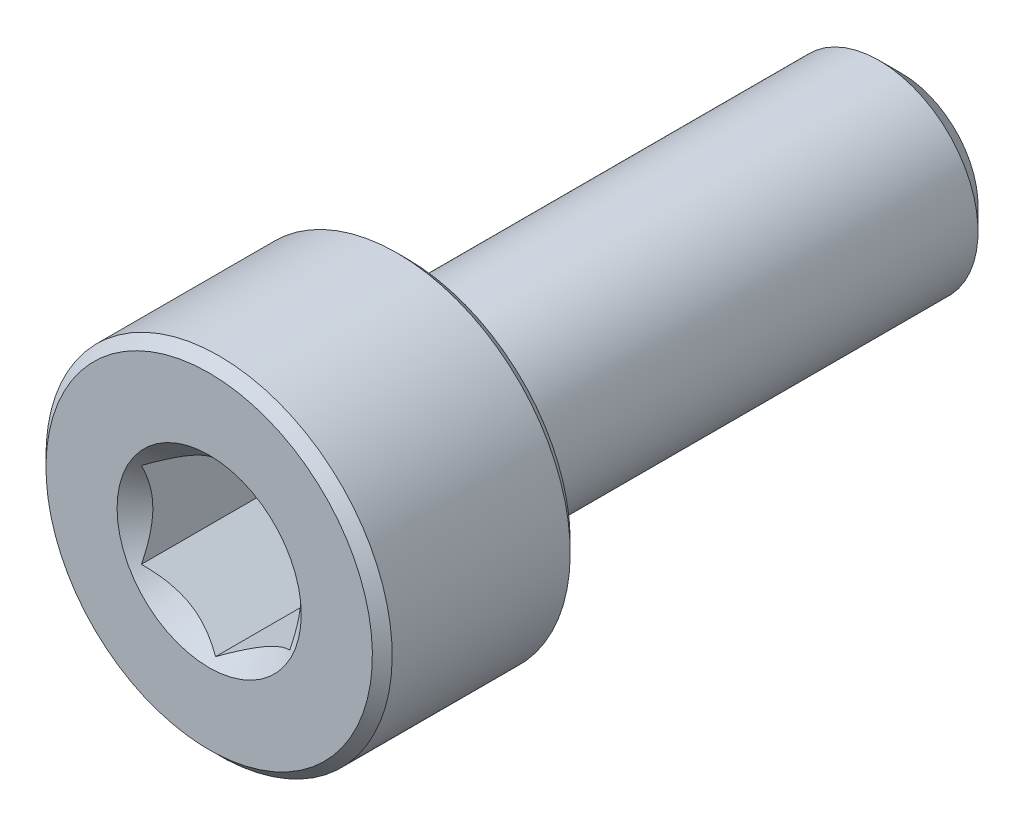
SolidWorks part; units mm, degrees
material "Plain Carbon Steel"
ref_plane "Front Plane" through (0, 0, 0) normal (0, 0, 1) x (1, 0, 0)
ref_plane "Top Plane" through (0, 0, 0) normal (0, 1, 0) x (1, 0, 0)
ref_plane "Right Plane" through (0, 0, 0) normal (1, 0, 0) x (0, 0, -1)
sketch "Sketch1" plane through (0, 0, 0) normal (1, 0, 0) x (0, 0, -1)
  line L0 (-7, 0) -> (7, 0) construction
  line L1 (7, 0) -> (7, 1.5453) construction
  line L2 (7, 1.5453) -> (6.5453, 2) construction
  line L3 (6.5453, 2) -> (6.475, 2) construction
  line L4 (6.475, 2) -> (-3, 2) construction
  line L5 (-3, 2) -> (-3, 3.5) construction
  line L6 (-3, 3.5) -> (-7, 3.5) construction
  line L7 (-7, 3.5) -> (-7, 0) construction
  line L8 (7, 1.5453) -> (7, 2) construction
  line L9 (6.9563, 2.0758) -> (7.3063, 1.4696) construction
  line L10 (7.3063, 1.4696) -> (7.6563, 2.0758) construction
  line L11 (7.6563, 2.0758) -> (6.9563, 2.0758) construction
  line L12 (7.3063, 2.0758) -> (7.3063, 2) construction
  line L13 (7.3063, 1.4696) -> (7.3063, 1.5453) construction
  line L14 (7.2625, 1.5453) -> (7.35, 1.5453) construction
  line L15 (7, 2) -> (7.6125, 2) construction
  line L16 (6.9781, 2.0379) -> (7.6344, 2.0379) construction
  line L17 (7, 0) -> (7, -2) construction
  line L18 (-3.2, 3.5) -> (-3, 3.3) construction
  line L19 (-6.8, 3.5) -> (-7, 3.3) construction
  line L20 (-3, 2) -> (-3, 0) construction
  line L21 (-3, 1) -> (0.3333, 1) construction
  line L22 (0.3333, 1) -> (3.6667, 1) construction
  line L23 (3.6667, 1) -> (7, 1) construction
  line L24 (0.3333, 1) -> (0.3333, 2) construction
  line L25 (0.3333, 2) -> (0.3333, 3.5) construction
  line L26 (3.6667, 1) -> (3.6667, 3.5) construction
  point P0 (-7, 1.5)
  point P3 (5.25, 2)
  point P4 (0, 0)
  point P18 (3.6667, 2)
  point P22 (7.3063, 1.5453)
  point P24 (6.475, 2)
  point P25 (7.3063, 2)
  point P28 (7.3063, 2.0379)
  point P29 (5.25, -2)
  point P30 (0.3333, 2)
  point P31 (-5, 3.5)
  point P37 (-3.7, 3.5)
  point P38 (-6.7, 3.5)
  point P45 (0.3333, 1)
  point P46 (3.6667, 1)
  dimension "D2" = 0.0875
  dimension "D7" = 0.2
  dimension "D8" = 0.2
  dimension "D9" = 0.2
  dimension "D10" = 0.1
  dimension "D11" = 0.5
  dimension "Drive Size" = 3
  dimension "Head Diameter" = 7
  dimension "Head Height" = 4
  dimension "Thread Pitch" = 0.7
  dimension "Thread Dia" = 4
  dimension "Length" = 10
  dimension "D12" = 0.525
  dimension "D4" = 1.75
  dimension "D3" = 45
sketch "Sketch2" plane through (0, 0, 0) normal (1, 0, 0) x (0, 0, -1)
  line L0 (-7, 0) -> (-7, 3.3)
  line L1 (-6.8, 3.5) -> (-3.2, 3.5)
  line L2 (-3, 3.3) -> (-3, 2.2)
  line L4 (6.5453, 2) -> (7, 1.5453)
  line L5 (7, 1.5453) -> (7, 0)
  line L6 (-3, 3.5) -> (-7, 3.5) construction
  line L7 (7, 0) -> (-7, 0)
  line L8 (-6.8, 3.5) -> (-7, 3.3) construction
  line L10 (-6.8, 3.5) -> (-7, 3.3)
  line L14 (-3.2, 3.5) -> (-3, 3.3) construction
  line L16 (-3.2, 3.5) -> (-3, 3.3)
  line L17 (-3, 2) -> (-3, 3.5) construction
  line L19 (-2.8, 2) -> (6.5453, 2)
  line L20 (6.475, 2) -> (-3, 2) construction
  arc A1 (-3, 2.2) -> (-2.8, 2) centre (-2.8, 2.2) ccw
  dimension "D3" = 0.2
revolve "Revolve1" add sketch "Sketch2" angle 360 about L7
sketch "Sketch3" plane through (0, 0, 7) normal (0, 0, 1) x (1, 0, 0)
  line L1 (1.5, -0.866) -> (1.5, 0.866)
  line L2 (1.5, 0.866) -> (0, 1.7321)
  line L3 (0, 1.7321) -> (-1.5, 0.866)
  line L4 (-1.5, 0.866) -> (-1.5, -0.866)
  line L5 (-1.5, -0.866) -> (0, -1.7321)
  line L6 (0, -1.7321) -> (1.5, -0.866)
  circle A0 centre (0, 0) radius 1.5 construction
  circle A1 centre (0, 0) radius 3.5 construction
  circle A2 centre (0, 0) radius 3.5 construction
  circle A3 centre (0, 0) radius 1.7321 construction
  point P13 (0, 0)
  dimension "D1" = 3.4641
extrude "Cut-Extrude1" cut sketch "Sketch3" against normal offset from surface (3 mm away) 1 up to face at (0, 3.3, 3)
sketch "Sketch4" plane through (0, 0, 7) normal (0, 0, 1) x (1, 0, 0)
  circle A0 centre (0, 0) radius 1.862
  dimension "D1" = 3.7239
extrude "Cut-Extrude2" cut sketch "Sketch4" against normal up to vertex (2 mm away) draft 45 up to point (0, 3.5, 5)
sketch "Sketch11" plane through (0, 0, 0) normal (1, 0, 0) x (0, 0, -1)
  line L0 (-7, 0) -> (7, 0) construction
  line L1 (-7, 0) -> (7, 0) construction
  line L2 (-1.125, 0) -> (-1.125, 2) construction
  line L3 (6.475, 2) -> (-3, 2) construction
  line L4 (5.125, 0) -> (5.125, 2) construction
  line L6 (7, 1.5453) -> (7, 2) construction
  point P2 (-1.125, 0)
  point P3 (5.125, 0)
  dimension "D1" = 1.875
  dimension "D2" = 1.875
sketch "Sketch6" [suppressed] plane through (0, 0, -7) normal (0, 0, -1) x (-1, 0, 0)
  circle A0 centre (0, 0) radius 2
curve "Helix/Spiral1" [suppressed] pitch 0.7 height 10.7 turns 15.2857
sketch "Sketch10" [suppressed] plane through (0, 0, 0) normal (1, 0, 0) x (0, 0, -1)
  line L0 (-2.8, -3.5) -> (-2.8, 3.5)
  line L5 (-7, 0) -> (7, 0) construction
  line L6 (-2.8, 2) -> (-2.8, -2) construction
  point P3 (-2.8, 0)
split "Split1" [suppressed] bodies to split 106
sketch "Sketch7" [suppressed] plane through (0, 0, 0) normal (1, 0, 0) x (0, 0, -1)
  line L0 (6.9781, 2.0379) -> (7.6344, 2.0379)
  line L1 (7.6344, 2.0379) -> (7.35, 1.5453)
  line L2 (7.35, 1.5453) -> (7.2625, 1.5453)
  line L3 (7.2625, 1.5453) -> (6.9781, 2.0379)
sweep "Cut-Sweep1" [suppressed] cut profiles "Sketch7" path "Helix/Spiral1"
sketch "Sketch8" [suppressed] plane through (0, 0, 0) normal (1, 0, 0) x (0, 0, -1)
  line L0 (-3, 0) -> (-3, 2)
  line L1 (-2.8, -2) -> (-2.8, 2) construction
  line L2 (-3, 2) -> (-2.8, 2)
  line L4 (-2.8, 2) -> (-1.6453, 0)
  line L5 (-1.6453, 0) -> (-3, 0)
  line L6 (6.475, 2) -> (-3, 2) construction
  line L7 (-7, 0) -> (7, 0) construction
  dimension "D1" = 60
revolve "Revolve2" [suppressed] add sketch "Sketch8" angle 360 about L5
equation "\"D2@Sketch1\" = \"Thread Pitch@Sketch1\" / 8"
equation "\"D4@Helix/Spiral1\" = \"Thread Pitch@Sketch1\""
equation "\"D7@Sketch1\" = \"Head Height@Sketch1\" * .05"
equation "\"D8@Sketch1\"=\"D7@Sketch1\""
equation "\"D9@Sketch1\"=\"D7@Sketch1\""
equation "\"D10@Sketch1\"=\"D7@Sketch1\"/2"
equation "\"D11@Sketch1\"=\"D10@Sketch1\"*5"
equation "\"D4@Sketch1\"=\"Thread Pitch@Sketch1\"*2.5"
equation "\"D12@Sketch1\"=\"Thread Pitch@Sketch1\"*.75"
equation "\"D3@Helix/Spiral1\"=\"Length@Sketch1\"+\"Thread Pitch@Sketch1\""
equation "\"D3@Sketch2\"=\"Thread Dia@Sketch1\"*0.05"
equation "\"D1@Sketch11\"=\"Length@Sketch1\"*0.1875"
equation "\"D2@Sketch11\"=\"D1@Sketch11\""
equation "\"D1@Sketch4\"=\"D1@Sketch3\"*1.075"
